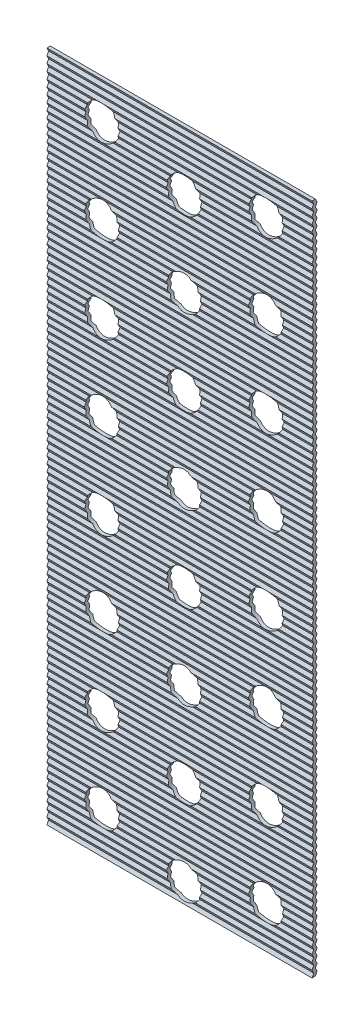
SolidWorks part; units mm, degrees
ref_plane "Спереди" through (0, 0, 0) normal (0, 0, 1) x (1, 0, 0)
ref_plane "Сверху" through (0, 0, 0) normal (0, 1, 0) x (1, 0, 0)
ref_plane "Справа" through (0, 0, 0) normal (1, 0, 0) x (0, 0, -1)
sketch "Эскиз1" plane through (0, 0, 0) normal (1, 0, 0) x (0, 0, -1)
  line L3 (1, 0) -> (0, 0)
  line L6 (0, 196) -> (0.5, 195)
  line L7 (0, 198) -> (0.5, 197)
  line L8 (1, 198) -> (1.5, 197)
  line L9 (1, 196) -> (1.5, 195)
  line L10 (0.5, 197) -> (0, 196)
  line L11 (1.5, 197) -> (1, 196)
  line L12 (0.5, 195) -> (0, 194)
  line L13 (1.5, 195) -> (1, 194)
  line L14 (0, 188) -> (0.5, 187)
  line L15 (0, 192) -> (0.5, 191)
  line L16 (0, 194) -> (0.5, 193)
  line L17 (1, 194) -> (1.5, 193)
  line L18 (1, 192) -> (1.5, 191)
  line L19 (0.5, 193) -> (0, 192)
  line L20 (1.5, 193) -> (1, 192)
  line L21 (0.5, 191) -> (0, 190)
  line L22 (1.5, 191) -> (1, 190)
  line L23 (0, 190) -> (0.5, 189)
  line L24 (1, 190) -> (1.5, 189)
  line L25 (1, 188) -> (1.5, 187)
  line L26 (0.5, 189) -> (0, 188)
  line L27 (1.5, 189) -> (1, 188)
  line L28 (0.5, 187) -> (0, 186)
  line L29 (1.5, 187) -> (1, 186)
  line L30 (0, 184) -> (0.5, 183)
  line L31 (0, 186) -> (0.5, 185)
  line L32 (1, 186) -> (1.5, 185)
  line L33 (1, 184) -> (1.5, 183)
  line L34 (0.5, 185) -> (0, 184)
  line L35 (1.5, 185) -> (1, 184)
  line L36 (0.5, 183) -> (0, 182)
  line L37 (1.5, 183) -> (1, 182)
  line L38 (0, 180) -> (0.5, 179)
  line L39 (0, 182) -> (0.5, 181)
  line L40 (1, 182) -> (1.5, 181)
  line L41 (1, 180) -> (1.5, 179)
  line L42 (0.5, 181) -> (0, 180)
  line L43 (1.5, 181) -> (1, 180)
  line L44 (0.5, 179) -> (0, 178)
  line L45 (1.5, 179) -> (1, 178)
  line L46 (0, 172) -> (0.5, 171)
  line L47 (0, 176) -> (0.5, 175)
  line L48 (0, 178) -> (0.5, 177)
  line L49 (1, 178) -> (1.5, 177)
  line L50 (1, 176) -> (1.5, 175)
  line L51 (0.5, 177) -> (0, 176)
  line L52 (1.5, 177) -> (1, 176)
  line L53 (0.5, 175) -> (0, 174)
  line L54 (1.5, 175) -> (1, 174)
  line L55 (0, 174) -> (0.5, 173)
  line L56 (1, 174) -> (1.5, 173)
  line L57 (1, 172) -> (1.5, 171)
  line L58 (0.5, 173) -> (0, 172)
  line L59 (1.5, 173) -> (1, 172)
  line L60 (0.5, 171) -> (0, 170)
  line L61 (1.5, 171) -> (1, 170)
  line L62 (0, 168) -> (0.5, 167)
  line L63 (0, 170) -> (0.5, 169)
  line L64 (1, 170) -> (1.5, 169)
  line L65 (1, 168) -> (1.5, 167)
  line L66 (0.5, 169) -> (0, 168)
  line L67 (1.5, 169) -> (1, 168)
  line L68 (0.5, 167) -> (0, 166)
  line L69 (1.5, 167) -> (1, 166)
  line L70 (0, 164) -> (0.5, 163)
  line L71 (0, 166) -> (0.5, 165)
  line L72 (1, 166) -> (1.5, 165)
  line L73 (1, 164) -> (1.5, 163)
  line L74 (0.5, 165) -> (0, 164)
  line L75 (1.5, 165) -> (1, 164)
  line L76 (0.5, 163) -> (0, 162)
  line L77 (1.5, 163) -> (1, 162)
  line L78 (0, 156) -> (0.5, 155)
  line L79 (0, 160) -> (0.5, 159)
  line L80 (0, 162) -> (0.5, 161)
  line L81 (1, 162) -> (1.5, 161)
  line L82 (1, 160) -> (1.5, 159)
  line L83 (0.5, 161) -> (0, 160)
  line L84 (1.5, 161) -> (1, 160)
  line L85 (0.5, 159) -> (0, 158)
  line L86 (1.5, 159) -> (1, 158)
  line L87 (0, 158) -> (0.5, 157)
  line L88 (1, 158) -> (1.5, 157)
  line L89 (1, 156) -> (1.5, 155)
  line L90 (0.5, 157) -> (0, 156)
  line L91 (1.5, 157) -> (1, 156)
  line L92 (0.5, 155) -> (0, 154)
  line L93 (1.5, 155) -> (1, 154)
  line L94 (0, 152) -> (0.5, 151)
  line L95 (0, 154) -> (0.5, 153)
  line L96 (1, 154) -> (1.5, 153)
  line L97 (1, 152) -> (1.5, 151)
  line L98 (0.5, 153) -> (0, 152)
  line L99 (1.5, 153) -> (1, 152)
  line L100 (0.5, 151) -> (0, 150)
  line L101 (1.5, 151) -> (1, 150)
  line L102 (0, 148) -> (0.5, 147)
  line L103 (0, 150) -> (0.5, 149)
  line L104 (1, 150) -> (1.5, 149)
  line L105 (1, 148) -> (1.5, 147)
  line L106 (0.5, 149) -> (0, 148)
  line L107 (1.5, 149) -> (1, 148)
  line L108 (0.5, 147) -> (0, 146)
  line L109 (1.5, 147) -> (1, 146)
  line L110 (0, 140) -> (0.5, 139)
  line L111 (0, 144) -> (0.5, 143)
  line L112 (0, 146) -> (0.5, 145)
  line L113 (1, 146) -> (1.5, 145)
  line L114 (1, 144) -> (1.5, 143)
  line L115 (0.5, 145) -> (0, 144)
  line L116 (1.5, 145) -> (1, 144)
  line L117 (0.5, 143) -> (0, 142)
  line L118 (1.5, 143) -> (1, 142)
  line L119 (0, 142) -> (0.5, 141)
  line L120 (1, 142) -> (1.5, 141)
  line L121 (1, 140) -> (1.5, 139)
  line L122 (0.5, 141) -> (0, 140)
  line L123 (1.5, 141) -> (1, 140)
  line L124 (0.5, 139) -> (0, 138)
  line L125 (1.5, 139) -> (1, 138)
  line L126 (0, 136) -> (0.5, 135)
  line L127 (0, 138) -> (0.5, 137)
  line L128 (1, 138) -> (1.5, 137)
  line L129 (1, 136) -> (1.5, 135)
  line L130 (0.5, 137) -> (0, 136)
  line L131 (1.5, 137) -> (1, 136)
  line L132 (0.5, 135) -> (0, 134)
  line L133 (1.5, 135) -> (1, 134)
  line L134 (0, 132) -> (0.5, 131)
  line L135 (0, 134) -> (0.5, 133)
  line L136 (1, 134) -> (1.5, 133)
  line L137 (1, 132) -> (1.5, 131)
  line L138 (0.5, 133) -> (0, 132)
  line L139 (1.5, 133) -> (1, 132)
  line L140 (0.5, 131) -> (0, 130)
  line L141 (1.5, 131) -> (1, 130)
  line L142 (0, 124) -> (0.5, 123)
  line L143 (0, 128) -> (0.5, 127)
  line L144 (0, 130) -> (0.5, 129)
  line L145 (1, 130) -> (1.5, 129)
  line L146 (1, 128) -> (1.5, 127)
  line L147 (0.5, 129) -> (0, 128)
  line L148 (1.5, 129) -> (1, 128)
  line L149 (0.5, 127) -> (0, 126)
  line L150 (1.5, 127) -> (1, 126)
  line L151 (0, 126) -> (0.5, 125)
  line L152 (1, 126) -> (1.5, 125)
  line L153 (1, 124) -> (1.5, 123)
  line L154 (0.5, 125) -> (0, 124)
  line L155 (1.5, 125) -> (1, 124)
  line L156 (0.5, 123) -> (0, 122)
  line L157 (1.5, 123) -> (1, 122)
  line L158 (0, 120) -> (0.5, 119)
  line L159 (0, 122) -> (0.5, 121)
  line L160 (1, 122) -> (1.5, 121)
  line L161 (1, 120) -> (1.5, 119)
  line L162 (0.5, 121) -> (0, 120)
  line L163 (1.5, 121) -> (1, 120)
  line L164 (0.5, 119) -> (0, 118)
  line L165 (1.5, 119) -> (1, 118)
  line L166 (0, 116) -> (0.5, 115)
  line L167 (0, 118) -> (0.5, 117)
  line L168 (1, 118) -> (1.5, 117)
  line L169 (1, 116) -> (1.5, 115)
  line L170 (0.5, 117) -> (0, 116)
  line L171 (1.5, 117) -> (1, 116)
  line L172 (0.5, 115) -> (0, 114)
  line L173 (1.5, 115) -> (1, 114)
  line L174 (0, 108) -> (0.5, 107)
  line L175 (0, 112) -> (0.5, 111)
  line L176 (0, 114) -> (0.5, 113)
  line L177 (1, 114) -> (1.5, 113)
  line L178 (1, 112) -> (1.5, 111)
  line L179 (0.5, 113) -> (0, 112)
  line L180 (1.5, 113) -> (1, 112)
  line L181 (0.5, 111) -> (0, 110)
  line L182 (1.5, 111) -> (1, 110)
  line L183 (0, 110) -> (0.5, 109)
  line L184 (1, 110) -> (1.5, 109)
  line L185 (1, 108) -> (1.5, 107)
  line L186 (0.5, 109) -> (0, 108)
  line L187 (1.5, 109) -> (1, 108)
  line L188 (0.5, 107) -> (0, 106)
  line L189 (1.5, 107) -> (1, 106)
  line L190 (0, 104) -> (0.5, 103)
  line L191 (0, 106) -> (0.5, 105)
  line L192 (1, 106) -> (1.5, 105)
  line L193 (1, 104) -> (1.5, 103)
  line L194 (0.5, 105) -> (0, 104)
  line L195 (1.5, 105) -> (1, 104)
  line L196 (0.5, 103) -> (0, 102)
  line L197 (1.5, 103) -> (1, 102)
  line L198 (0, 100) -> (0.5, 99)
  line L199 (0, 102) -> (0.5, 101)
  line L200 (1, 102) -> (1.5, 101)
  line L201 (1, 100) -> (1.5, 99)
  line L202 (0.5, 101) -> (0, 100)
  line L203 (1.5, 101) -> (1, 100)
  line L204 (0.5, 99) -> (0, 98)
  line L205 (1.5, 99) -> (1, 98)
  line L206 (0, 92) -> (0.5, 91)
  line L207 (0, 96) -> (0.5, 95)
  line L208 (0, 98) -> (0.5, 97)
  line L209 (1, 98) -> (1.5, 97)
  line L210 (1, 96) -> (1.5, 95)
  line L211 (0.5, 97) -> (0, 96)
  line L212 (1.5, 97) -> (1, 96)
  line L213 (0.5, 95) -> (0, 94)
  line L214 (1.5, 95) -> (1, 94)
  line L215 (0, 94) -> (0.5, 93)
  line L216 (1, 94) -> (1.5, 93)
  line L217 (1, 92) -> (1.5, 91)
  line L218 (0.5, 93) -> (0, 92)
  line L219 (1.5, 93) -> (1, 92)
  line L220 (0.5, 91) -> (0, 90)
  line L221 (1.5, 91) -> (1, 90)
  line L222 (0, 88) -> (0.5, 87)
  line L223 (0, 90) -> (0.5, 89)
  line L224 (1, 90) -> (1.5, 89)
  line L225 (1, 88) -> (1.5, 87)
  line L226 (0.5, 89) -> (0, 88)
  line L227 (1.5, 89) -> (1, 88)
  line L228 (0.5, 87) -> (0, 86)
  line L229 (1.5, 87) -> (1, 86)
  line L230 (0, 84) -> (0.5, 83)
  line L231 (0, 86) -> (0.5, 85)
  line L232 (1, 86) -> (1.5, 85)
  line L233 (1, 84) -> (1.5, 83)
  line L234 (0.5, 85) -> (0, 84)
  line L235 (1.5, 85) -> (1, 84)
  line L236 (0.5, 83) -> (0, 82)
  line L237 (1.5, 83) -> (1, 82)
  line L238 (0, 76) -> (0.5, 75)
  line L239 (0, 80) -> (0.5, 79)
  line L240 (0, 82) -> (0.5, 81)
  line L241 (1, 82) -> (1.5, 81)
  line L242 (1, 80) -> (1.5, 79)
  line L243 (0.5, 81) -> (0, 80)
  line L244 (1.5, 81) -> (1, 80)
  line L245 (0.5, 79) -> (0, 78)
  line L246 (1.5, 79) -> (1, 78)
  line L247 (0, 78) -> (0.5, 77)
  line L248 (1, 78) -> (1.5, 77)
  line L249 (1, 76) -> (1.5, 75)
  line L250 (0.5, 77) -> (0, 76)
  line L251 (1.5, 77) -> (1, 76)
  line L252 (0.5, 75) -> (0, 74)
  line L253 (1.5, 75) -> (1, 74)
  line L254 (0, 72) -> (0.5, 71)
  line L255 (0, 74) -> (0.5, 73)
  line L256 (1, 74) -> (1.5, 73)
  line L257 (1, 72) -> (1.5, 71)
  line L258 (0.5, 73) -> (0, 72)
  line L259 (1.5, 73) -> (1, 72)
  line L260 (0.5, 71) -> (0, 70)
  line L261 (1.5, 71) -> (1, 70)
  line L262 (0, 68) -> (0.5, 67)
  line L263 (0, 70) -> (0.5, 69)
  line L264 (1, 70) -> (1.5, 69)
  line L265 (1, 68) -> (1.5, 67)
  line L266 (0.5, 69) -> (0, 68)
  line L267 (1.5, 69) -> (1, 68)
  line L268 (0.5, 67) -> (0, 66)
  line L269 (1.5, 67) -> (1, 66)
  line L270 (0, 60) -> (0.5, 59)
  line L271 (0, 64) -> (0.5, 63)
  line L272 (0, 66) -> (0.5, 65)
  line L273 (1, 66) -> (1.5, 65)
  line L274 (1, 64) -> (1.5, 63)
  line L275 (0.5, 65) -> (0, 64)
  line L276 (1.5, 65) -> (1, 64)
  line L277 (0.5, 63) -> (0, 62)
  line L278 (1.5, 63) -> (1, 62)
  line L279 (0, 62) -> (0.5, 61)
  line L280 (1, 62) -> (1.5, 61)
  line L281 (1, 60) -> (1.5, 59)
  line L282 (0.5, 61) -> (0, 60)
  line L283 (1.5, 61) -> (1, 60)
  line L284 (0.5, 59) -> (0, 58)
  line L285 (1.5, 59) -> (1, 58)
  line L286 (0, 56) -> (0.5, 55)
  line L287 (0, 58) -> (0.5, 57)
  line L288 (1, 58) -> (1.5, 57)
  line L289 (1, 56) -> (1.5, 55)
  line L290 (0.5, 57) -> (0, 56)
  line L291 (1.5, 57) -> (1, 56)
  line L292 (0.5, 55) -> (0, 54)
  line L293 (1.5, 55) -> (1, 54)
  line L294 (0, 52) -> (0.5, 51)
  line L295 (0, 54) -> (0.5, 53)
  line L296 (1, 54) -> (1.5, 53)
  line L297 (1, 52) -> (1.5, 51)
  line L298 (0.5, 53) -> (0, 52)
  line L299 (1.5, 53) -> (1, 52)
  line L300 (0.5, 51) -> (0, 50)
  line L301 (1.5, 51) -> (1, 50)
  line L302 (0, 44) -> (0.5, 43)
  line L303 (0, 48) -> (0.5, 47)
  line L304 (0, 50) -> (0.5, 49)
  line L305 (1, 50) -> (1.5, 49)
  line L306 (1, 48) -> (1.5, 47)
  line L307 (0.5, 49) -> (0, 48)
  line L308 (1.5, 49) -> (1, 48)
  line L309 (0.5, 47) -> (0, 46)
  line L310 (1.5, 47) -> (1, 46)
  line L311 (0, 46) -> (0.5, 45)
  line L312 (1, 46) -> (1.5, 45)
  line L313 (1, 44) -> (1.5, 43)
  line L314 (0.5, 45) -> (0, 44)
  line L315 (1.5, 45) -> (1, 44)
  line L316 (0.5, 43) -> (0, 42)
  line L317 (1.5, 43) -> (1, 42)
  line L318 (0, 40) -> (0.5, 39)
  line L319 (0, 42) -> (0.5, 41)
  line L320 (1, 42) -> (1.5, 41)
  line L321 (1, 40) -> (1.5, 39)
  line L322 (0.5, 41) -> (0, 40)
  line L323 (1.5, 41) -> (1, 40)
  line L324 (0.5, 39) -> (0, 38)
  line L325 (1.5, 39) -> (1, 38)
  line L326 (0, 36) -> (0.5, 35)
  line L327 (0, 38) -> (0.5, 37)
  line L328 (1, 38) -> (1.5, 37)
  line L329 (1, 36) -> (1.5, 35)
  line L330 (0.5, 37) -> (0, 36)
  line L331 (1.5, 37) -> (1, 36)
  line L332 (0.5, 35) -> (0, 34)
  line L333 (1.5, 35) -> (1, 34)
  line L334 (0, 28) -> (0.5, 27)
  line L335 (0, 32) -> (0.5, 31)
  line L336 (0, 34) -> (0.5, 33)
  line L337 (1, 34) -> (1.5, 33)
  line L338 (1, 32) -> (1.5, 31)
  line L339 (0.5, 33) -> (0, 32)
  line L340 (1.5, 33) -> (1, 32)
  line L341 (0.5, 31) -> (0, 30)
  line L342 (1.5, 31) -> (1, 30)
  line L343 (0, 30) -> (0.5, 29)
  line L344 (1, 30) -> (1.5, 29)
  line L345 (1, 28) -> (1.5, 27)
  line L346 (0.5, 29) -> (0, 28)
  line L347 (1.5, 29) -> (1, 28)
  line L348 (0.5, 27) -> (0, 26)
  line L349 (1.5, 27) -> (1, 26)
  line L350 (0, 24) -> (0.5, 23)
  line L351 (0, 26) -> (0.5, 25)
  line L352 (1, 26) -> (1.5, 25)
  line L353 (1, 24) -> (1.5, 23)
  line L354 (0.5, 25) -> (0, 24)
  line L355 (1.5, 25) -> (1, 24)
  line L356 (0.5, 23) -> (0, 22)
  line L357 (1.5, 23) -> (1, 22)
  line L358 (0, 20) -> (0.5, 19)
  line L359 (0, 22) -> (0.5, 21)
  line L360 (1, 22) -> (1.5, 21)
  line L361 (1, 20) -> (1.5, 19)
  line L362 (0.5, 21) -> (0, 20)
  line L363 (1.5, 21) -> (1, 20)
  line L364 (0.5, 19) -> (0, 18)
  line L365 (1.5, 19) -> (1, 18)
  line L366 (0, 12) -> (0.5, 11)
  line L367 (0, 16) -> (0.5, 15)
  line L368 (0, 18) -> (0.5, 17)
  line L369 (1, 18) -> (1.5, 17)
  line L370 (1, 16) -> (1.5, 15)
  line L371 (0.5, 17) -> (0, 16)
  line L372 (1.5, 17) -> (1, 16)
  line L373 (0.5, 15) -> (0, 14)
  line L374 (1.5, 15) -> (1, 14)
  line L375 (0, 14) -> (0.5, 13)
  line L376 (1, 14) -> (1.5, 13)
  line L377 (1, 12) -> (1.5, 11)
  line L378 (0.5, 13) -> (0, 12)
  line L379 (1.5, 13) -> (1, 12)
  line L380 (0.5, 11) -> (0, 10)
  line L381 (1.5, 11) -> (1, 10)
  line L382 (0, 8) -> (0.5, 7)
  line L383 (0, 10) -> (0.5, 9)
  line L384 (1, 10) -> (1.5, 9)
  line L385 (1, 8) -> (1.5, 7)
  line L386 (0.5, 9) -> (0, 8)
  line L387 (1.5, 9) -> (1, 8)
  line L388 (0.5, 7) -> (0, 6)
  line L389 (1.5, 7) -> (1, 6)
  line L390 (0, 4) -> (0.5, 3)
  line L391 (0, 6) -> (0.5, 5)
  line L392 (1, 6) -> (1.5, 5)
  line L393 (1, 4) -> (1.5, 3)
  line L394 (0.5, 5) -> (0, 4)
  line L395 (1.5, 5) -> (1, 4)
  line L396 (0.5, 3) -> (0, 2)
  line L397 (1.5, 3) -> (1, 2)
  line L398 (0, 198) -> (1, 198)
  line L400 (0, 2) -> (0.5, 1)
  line L401 (1, 2) -> (1.5, 1)
  line L403 (0.5, 1) -> (0, 0)
  line L404 (1.5, 1) -> (1, 0)
extrude "Бобышка-Вытянуть1" add sketch "Эскиз1" along normal blind 78
ref_plane "Плоскость1" through (0, 121, -1.5) normal (-1, 0, 0) x (0, 0, 1)
sketch "Эскиз3" plane through (0, 0, 0) normal (0, 0, 1) x (1, 0, 0)
  circle A0 centre (16, 12) radius 5
  circle A1 centre (16, 37) radius 5
  circle A2 centre (40.1481, 30.5295) radius 5
  circle A3 centre (40.1481, 55.5295) radius 5
  circle A4 centre (64.2963, 37) radius 5
  circle A5 centre (64.2963, 62) radius 5
  circle A6 centre (16, 62) radius 5
  circle A7 centre (64.2963, 12) radius 5
  circle A8 centre (40.1481, 5.5295) radius 5
  circle A9 centre (64.2963, 87) radius 5
  circle A10 centre (40.1481, 80.5295) radius 5
  circle A11 centre (16, 87) radius 5
  circle A12 centre (16, 112) radius 5
  circle A13 centre (40.1481, 105.5295) radius 5
  circle A14 centre (64.2963, 112) radius 5
  circle A15 centre (64.2963, 137) radius 5
  circle A16 centre (40.1481, 130.5295) radius 5
  circle A17 centre (16, 137) radius 5
  circle A18 centre (16, 162) radius 5
  circle A19 centre (40.1481, 155.5295) radius 5
  circle A20 centre (64.2963, 162) radius 5
  circle A21 centre (64.2963, 187) radius 5
  circle A22 centre (40.1481, 180.5295) radius 5
  circle A23 centre (16, 187) radius 5
extrude "Вырез-Вытянуть1" cut sketch "Эскиз3" against normal blind 10 and the other way blind 10
